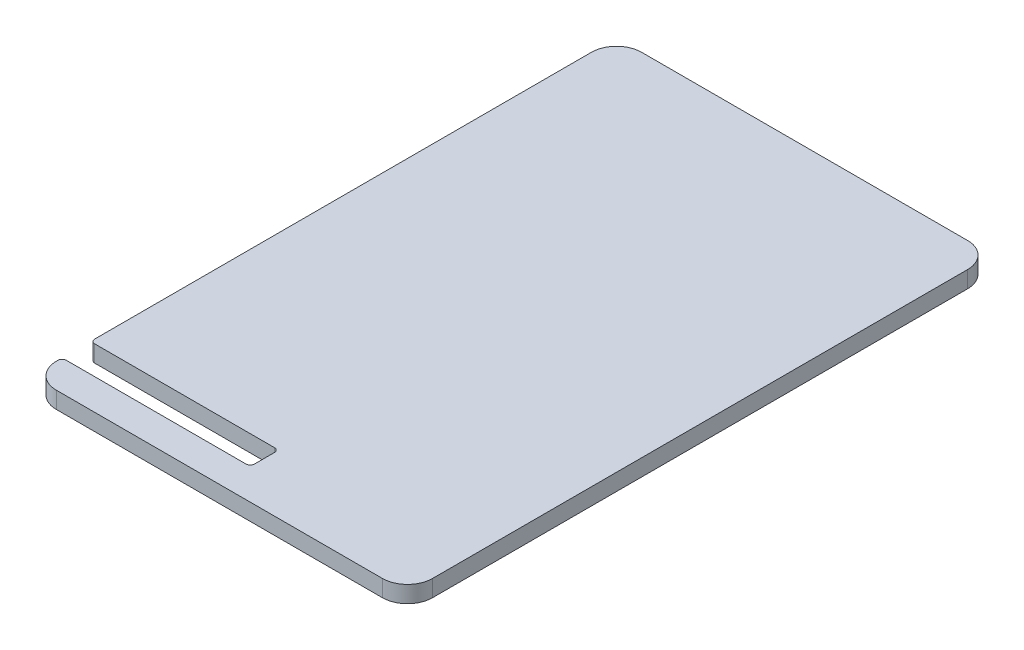
SolidWorks part; units mm, degrees
ref_plane "Alzado" through (0, 0, 0) normal (0, 0, 1) x (1, 0, 0)
ref_plane "Planta" through (0, 0, 0) normal (0, 1, 0) x (1, 0, 0)
ref_plane "Vista lateral" through (0, 0, 0) normal (1, 0, 0) x (0, 0, -1)
sketch "Croquis1" plane through (0, 0, 0) normal (0, 1, 0) x (1, 0, 0)
  line L1 (-22.5, 35.3062) -> (22.5, 35.3062)
  line L2 (-22.5, 35.3062) -> (-22.5, -34.6938)
  line L3 (-22.5, -34.6938) -> (22.5, -34.6938)
  line L4 (22.5, 35.3062) -> (22.5, -34.6938)
  dimension "D1" = 22.5
  dimension "D2" = 45
  dimension "D3" = 35.3062
  dimension "D4" = 70
extrude "Saliente-Extruir1" add sketch "Croquis1" along normal blind 2
sketch "Croquis2" plane through (0, 2, 0) normal (0, 1, 0) x (1, 0, 0)
  line L0 (-22.5, 35.3062) -> (-22.5, -34.6938) construction
  line L1 (-22.5, -27.6) -> (0, -27.6)
  line L2 (-22.5, -27.6) -> (-22.5, -31)
  line L3 (-22.5, -31) -> (0, -31)
  line L4 (0, -27.6) -> (0, -31)
  dimension "D1" = 3.4
  dimension "D2" = 31
  dimension "D3" = 22.5
extrude "Cortar-Extruir1" cut sketch "Croquis2" against normal up to surface (2 mm away) up to face at (0, 0, -0.3062)
fillet "Redondeo1" radius 3 4 edges at (-22.5, 1, 34.6938) (22.5, 1, 34.6938) (-22.5, 1, -35.3062) (22.5, 1, -35.3062)
fillet "Redondeo2" radius 0.5 4 edges at (-22.5, 1, 31) (0, 1, 31) (0, 1, 27.6) (-22.5, 1, 27.6)
